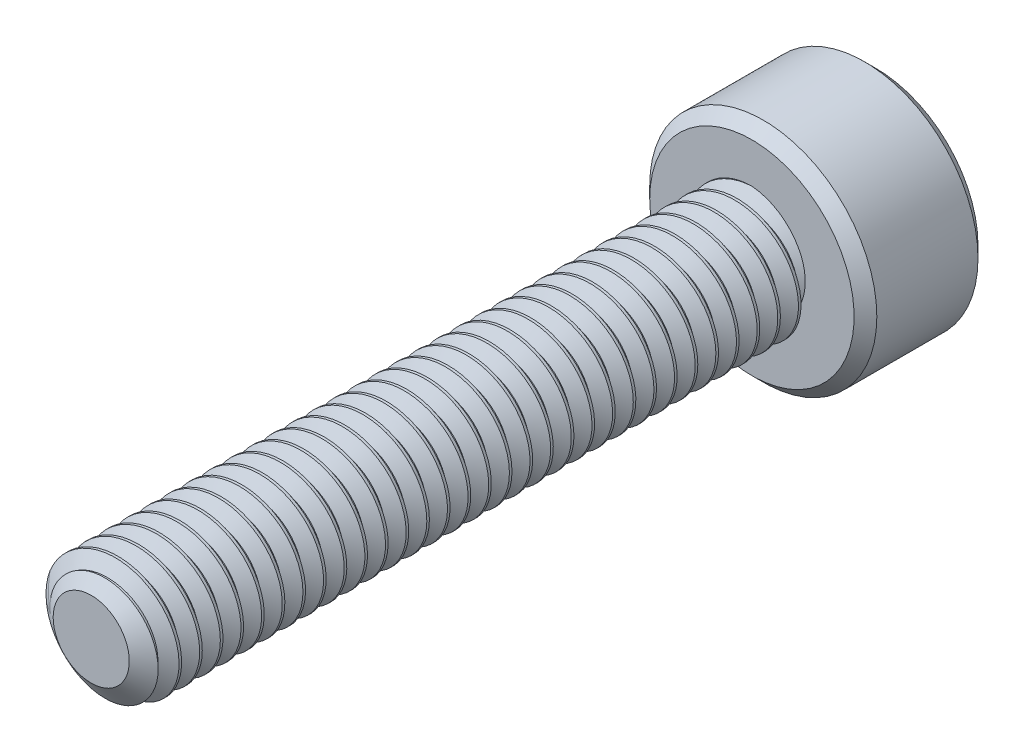
SolidWorks part; units mm, degrees
other "DetailItem1"
ref_plane "Front Plane" through (0, 0, 0) normal (0, 0, 1) x (1, 0, 0)
ref_plane "Top Plane" through (0, 0, 0) normal (0, 1, 0) x (1, 0, 0)
ref_plane "Right Plane" through (0, 0, 0) normal (1, 0, 0) x (0, 0, -1)
sketch "Sketch1" plane through (0, 0, 0) normal (0, 0, 1) x (1, 0, 0)
  circle A0 centre (0, 0) radius 1.5
  dimension "OD" = 3
extrude "Extrude1" add sketch "Sketch1" against normal blind 16
sketch "Sketch2" plane through (0, 0, 0) normal (0, 0, 1) x (1, 0, 0)
  circle A0 centre (0, 0) radius 1.5 construction
  circle A1 centre (0, 0) radius 1.5
curve "Helix/Spiral1" pitch 0.5 height 16.5 turns 33 parameters "pitch"=0.5
sketch "Sketch3" plane through (0, 0, 0) normal (1, 0, 0) x (0, 0, -1)
  line L0 (-0.4375, 1.5) -> (-0.25, 1.1752)
  line L1 (-0.25, 1.1752) -> (-0.1875, 1.1752)
  line L2 (-0.1875, 1.1752) -> (0, 1.5)
  line L3 (-0.4375, 1.5) -> (0, 1.5)
  line L4 (-0.2187, 1.5) -> (-0.2188, 1.1752) construction
  line L5 (-0.3438, 1.3376) -> (-0.0938, 1.3376) construction
  line L6 (0, 1.5) -> (0, -1.5) construction
  dimension "D1" = 0.0625
  dimension "D2" = 0.25
  dimension "D3" = 60
sweep "Cut-Sweep1" cut profiles "Sketch3" path "Helix/Spiral1"
sketch "Sketch4" plane through (0, 0, 0) normal (1, 0, 0) x (0, 0, -1)
  line L0 (0.4053, 1.5) -> (0, 0.9212)
  line L1 (0, 0.9212) -> (0, 1.5)
  line L2 (0.4053, 1.5) -> (0, 1.5)
  line L3 (-0.4375, 1.5) -> (0, 1.5) construction
  line L4 (0, 0) -> (7.0209, 0) construction
  dimension "D1" = 55
  dimension "D2" = 0.254
revolve "Cut-Revolve1" cut sketch "Sketch4" angle 360 about L4
sketch "Sketch6" plane through (0, 0, -16) normal (0, 0, -1) x (-1, 0, 0)
  circle A0 centre (0, 0) radius 2.75
  dimension "head dia" = 5.5
extrude "Extrude2" add sketch "Sketch6" along normal blind 3
sketch "Sketch7" plane through (0, 0, -19) normal (0, 0, -1) x (-1, 0, 0)
  line L1 (0, 1.4434) -> (-1.25, 0.7217)
  line L2 (-1.25, 0.7217) -> (-1.25, -0.7217)
  line L3 (-1.25, -0.7217) -> (0, -1.4434)
  line L4 (0, -1.4434) -> (1.25, -0.7217)
  line L5 (1.25, -0.7217) -> (1.25, 0.7217)
  line L6 (1.25, 0.7217) -> (0, 1.4434)
  circle A0 centre (0, 0) radius 1.25 construction
  dimension "hex dia" = 2.5
extrude "Cut-Extrude1" cut sketch "Sketch7" against normal blind 1.875
sketch "Sketch8" plane through (0, 0, -19) normal (0, 0, -1) x (-1, 0, 0)
  circle A0 centre (0, 0) radius 1.4434
extrude "Cut-Extrude2" cut sketch "Sketch8" against normal through all draft 45
chamfer "Chamfer1" distance 0.275 angle 45 2 edges at (-2.75, 0, -19) (-2.75, 0, -16)
sketch "Sketch10" plane through (0, 0, -16) normal (0, 0, 1) x (1, 0, 0)
  circle A1 centre (0, 0) radius 1.5
  circle A2 centre (0, 0) radius 1.5
  dimension "D1" = 0
ref_plane "Plane1" through (0, 0, 0) normal (0, 0, 1) x (1, 0, 0)
extrude "partial thread" [suppressed] add sketch "Sketch10" along normal up to surface (4 mm away) separate body
chamfer "Chamfer2" [suppressed] distance 0.06 angle 45
combine bodies "Combine1" [suppressed] operation type add bodies to combine 107 108
sketch "Sketch9" plane through (0, 0, 0) normal (1, 0, 0) x (0, 0, -1)
  line L0 (0, 1.5) -> (0, -1.5) construction
  line L1 (1.25, 1.5) -> (1.25, -1.5) construction
  dimension "D1" = 1.25
equation "\"D3@Helix/Spiral1\" = \"screw length@Extrude1\"+\"pitch@Helix/Spiral1\""
equation "\"D1@Sketch3\" = \"pitch@Helix/Spiral1\"*.125"
equation "\"D2@Sketch3\" = \"pitch@Helix/Spiral1\"*.5"
equation "\"D1@Cut-Extrude1\" = \"hex dia@Sketch7\"*.75"
equation "\"D1@Chamfer1\" = \"head dia@Sketch6\"*.05"
equation "\"D1@Sketch9\" = \"pitch@Helix/Spiral1\"*2.5"
equation "\"D1@Chamfer2\"=\"OD@Sketch1\"*.02"
